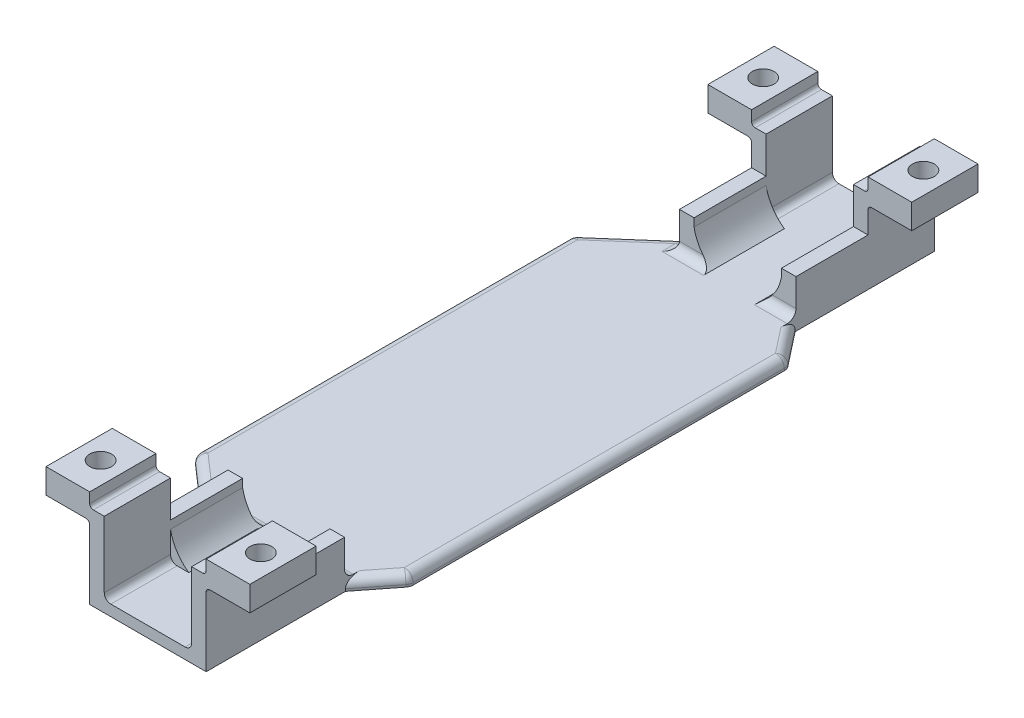
SolidWorks part; units mm, degrees
ref_plane "Front Plane" through (0, 0, 0) normal (0, 0, 1) x (1, 0, 0)
ref_plane "Top Plane" through (0, 0, 0) normal (0, 1, 0) x (1, 0, 0)
ref_plane "Right Plane" through (0, 0, 0) normal (1, 0, 0) x (0, 0, -1)
sketch "Sketch2" plane through (0, 0, 0) normal (0, 1, 0) x (1, 0, 0)
  line L1 (-8, -9.5) -> (8, -9.5)
  line L2 (-8, -9.5) -> (-8, 9.5)
  line L3 (-8, 9.5) -> (8, 9.5)
  line L4 (8, -9.5) -> (8, 9.5)
  line L5 (-8, -9.5) -> (8, 9.5) construction
  line L6 (-8, 9.5) -> (8, -9.5) construction
  point P0 (0, 0)
  dimension "D1" = 16
  dimension "D2" = 19
extrude "Boss-Extrude1" add sketch "Sketch2" along normal blind 13.3
sketch "Sketch3" plane through (0, 13.3, 0) normal (0, 1, 0) x (1, 0, 0)
  line L0 (8, 9.5) -> (-8, 9.5) construction
  line L1 (-6, -9.5) -> (6, -9.5)
  line L2 (-6, -9.5) -> (-6, 9.5)
  line L3 (-6, 9.5) -> (6, 9.5)
  line L4 (6, -9.5) -> (6, 9.5)
  line L5 (-6, -9.5) -> (6, 9.5) construction
  line L6 (-6, 9.5) -> (6, -9.5) construction
  point P0 (0, 0)
  dimension "D1" = 12
extrude "Cut-Extrude1" cut sketch "Sketch3" against normal blind 8.9
fillet "Fillet1" radius 2 2 edges at (-8, 13.3, 0) (8, 13.3, 0)
sketch "Sketch4" plane through (0, 0, 0) normal (1, 0, 0) x (0, 0, -1)
  line L0 (8.8, 0) -> (-8.8, 0) construction
  line L1 (-9.5, 13.3) -> (0.4, 13.3)
  line L2 (-9.5, 13.3) -> (-9.5, 9.4)
  line L3 (-9.5, 9.4) -> (0.4, 9.4)
  line L4 (0.4, 13.3) -> (0.4, 9.4)
  dimension "D1" = 9.9
  dimension "D2" = 9.4
extrude "Cut-Extrude2" cut sketch "Sketch4" against normal through all both and the other way through all
sketch "Sketch5" plane through (0, 0, 0) normal (1, 0, 0) x (0, 0, -1)
  line L0 (8.8, 0) -> (-8.8, 0) construction
  line L1 (-7, 2.7) -> (-3.2, 2.7)
  line L2 (-7, 2.7) -> (-7, 1)
  line L3 (-7, 1) -> (-3.2, 1)
  line L4 (-3.2, 2.7) -> (-3.2, 1)
  line L5 (-9.5, 9.4) -> (-9.5, 0) construction
  dimension "D1" = 3.8
  dimension "D2" = 1.7
  dimension "D3" = 1
  dimension "D4" = 2.5
extrude "Cut-Extrude3" cut sketch "Sketch5" against normal through all both and the other way through all
sketch "Sketch6" plane through (0, 0, 0) normal (0, 1, 0) x (1, 0, 0)
  line L0 (6, 9.5) -> (-6, 9.5) construction
  line L1 (-14, 9.5) -> (14, 9.5)
  line L2 (0, 9.5) -> (0, 0.4)
  line L3 (-14, 0.4) -> (14, 0.4)
  line L4 (14, 9.5) -> (14, 0.4)
  line L6 (0, -3.575) -> (0, 3.575) construction
  line L7 (-14, 9.5) -> (-14, 0.4)
  dimension "D1" = 9.1
  dimension "D2" = 14
extrude "Boss-Extrude2" add sketch "Sketch6" along normal blind 2.5 contours L4 L1 L2 L3 | L1 L7 L3 L2
sketch "Sketch7" plane through (0, 2.5, 0) normal (0, 1, 0) x (1, 0, 0)
  line L0 (-8, 9.5) -> (-8, 0.4) construction
  line L1 (-14, 9.5) -> (-8, 9.5) construction
  line L2 (0, -3.575) -> (0, 3.575) construction
  line L3 (-14, 9.5) -> (-14, 0.4) construction
  circle A0 centre (-11, 5) radius 1.55
  circle A1 centre (11, 5) radius 1.55
  dimension "D1" = 3.1
  dimension "D2" = 3
  dimension "D3" = 4.5
  dimension "D4" = 3
extrude "Cut-Extrude4" cut sketch "Sketch7" against normal through all both and the other way through all
sketch "Sketch14" plane through (0, 0, 0) normal (0, 0, 1) x (1, 0, 0)
  line L1 (-6, 13.3) -> (6, 13.3)
  line L2 (-6, 13.3) -> (-6, 4.4)
  line L3 (-6, 4.4) -> (6, 4.4)
  line L4 (6, 13.3) -> (6, 4.4)
extrude "Boss-Extrude3" add sketch "Sketch14" along normal blind 9.5
sketch "Sketch16" plane through (0, 0, 0) normal (0, 1, 0) x (1, 0, 0)
  line L1 (-14, 9.5) -> (14, 9.5)
  line L2 (-14, 9.5) -> (-14, 0.4)
  line L3 (-14, 0.4) -> (14, 0.4)
  line L4 (14, 9.5) -> (14, 0.4)
extrude "Cut-Extrude10" cut sketch "Sketch16" along normal through all both and the other way through all
sketch "Sketch17" plane through (0, 0, 0) normal (0, 1, 0) x (1, 0, 0)
  line L1 (-8, -9.5) -> (8, -9.5)
  line L2 (-8, -9.5) -> (-8, -71.5)
  line L3 (-8, -71.5) -> (8, -71.5)
  line L4 (8, -9.5) -> (8, -71.5)
  dimension "D1" = 62
  dimension "D2" = 16
extrude "Boss-Extrude5" add sketch "Sketch17" along normal blind 4.4
sketch "Sketch22" plane through (0, 0, 0) normal (0, 1, 0) x (1, 0, 0)
  line L0 (-3.575, 0) -> (3.575, 0) construction
  line L1 (-6, 0.4) -> (6.0328, 0.4)
  line L2 (-6, 0.4) -> (-6, 0)
  line L3 (-6, 0) -> (6.0328, 0)
  line L4 (6.0328, 0.4) -> (6.0328, 0)
extrude "Boss-Extrude7" add sketch "Sketch22" along normal blind 9.4
sketch "Sketch20" plane through (0, 0, 0) normal (0, 1, 0) x (1, 0, 0)
  line L1 (-8, -71.5) -> (8, -71.5)
  line L2 (-8, -71.5) -> (-8, -81.4)
  line L3 (-8, -81.4) -> (8, -81.4)
  line L4 (8, -71.5) -> (8, -81.4)
  dimension "D1" = 9.9
  dimension "D2" = 16
extrude "Boss-Extrude6" add sketch "Sketch20" along normal blind 9.4
sketch "Sketch24" plane through (0, 0, 0) normal (0, 1, 0) x (1, 0, 0)
  line L1 (-8, -81.4) -> (8, -81.4)
  line L2 (-8, -81.4) -> (-8, -90.5)
  line L3 (-8, -90.5) -> (8, -90.5)
  line L4 (8, -81.4) -> (8, -90.5)
  line L5 (8, 0.4) -> (-8, 0.4)
  line L6 (8, 0.4) -> (8, 9.5)
  line L7 (8, 9.5) -> (-8, 9.5)
  line L8 (-8, 0.4) -> (-8, 9.5)
  dimension "D1" = 9.1
  dimension "D2" = 16
  dimension "D3" = 9.1
  dimension "D4" = 16
extrude "Boss-Extrude8" add sketch "Sketch24" along normal blind 4.4
sketch "Sketch21" plane through (0, 0, 0) normal (1, 0, 0) x (0, 0, -1)
  line L0 (8.8, 0) -> (-8.8, 0) construction
  line L1 (-81.4, 0) -> (918.6, 0)
  line L2 (-81.4, 0) -> (-81.4, 2.9)
  line L3 (-81.4, 2.9) -> (918.6, 2.9)
  line L4 (918.6, 0) -> (918.6, 2.9)
  line L5 (-81.4, 9.4) -> (-81.4, 4.4) construction
  line L6 (-71.5, 4.4) -> (-9.5, 4.4) construction
  dimension "D1" = 1.5
  dimension "D2" = 1000
extrude "Cut-Extrude11" cut sketch "Sketch21" against normal through all both and the other way through all
sketch "Sketch15" plane through (0, 0, 0) normal (0, 0, 1) x (1, 0, 0)
  line L0 (0, -3.575) -> (0, 3.575) construction
  line L1 (-6, 4.4) -> (6, 4.4) construction
  line L2 (-6, 4.4) -> (6, 4.4)
  line L7 (-6, 13.3) -> (6, 13.3)
  line L8 (-6, 13.3) -> (-6, 9.4)
  line L9 (-6, 9.4) -> (6, 9.4)
  line L10 (6, 13.3) -> (6, 9.4)
  line L11 (6, 13.3) -> (6, 4.4)
  line L12 (6, 13.3) -> (6, 4.4)
  line L13 (-6, 13.3) -> (-6, 4.4)
  circle A0 centre (0, 9.4) radius 6.1
  dimension "D1" = 12.2
  dimension "D2" = 5
extrude "Cut-Extrude9" cut sketch "Sketch15" against normal blind 1000 and the other way blind 81.4 contours L7 A0 | L9 A0 L7 | L9 A0 L2 | A0 L7 L8
sketch "Sketch25" plane through (0, 4.4, 0) normal (0, 1, 0) x (1, 0, 0)
  line L0 (6, 0.4) -> (8, 0.4) construction
  line L1 (8, -90.5) -> (6, -90.5)
  line L2 (8, -90.5) -> (8, -81.4)
  line L3 (8, -81.4) -> (6, -81.4)
  line L4 (6, -90.5) -> (6, -81.4)
  line L5 (-8, -90.5) -> (-6, -90.5)
  line L6 (-8, -90.5) -> (-8, -81.4)
  line L7 (-8, -81.4) -> (-6, -81.4)
  line L8 (-6, -90.5) -> (-6, -81.4)
  line L9 (-8, 9.5) -> (-6, 9.5)
  line L10 (-8, 9.5) -> (-8, 0.4)
  line L11 (-8, 0.4) -> (-6, 0.4)
  line L12 (-6, 9.5) -> (-6, 0.4)
  line L13 (8, 9.5) -> (6, 9.5)
  line L14 (8, 9.5) -> (8, 0.4)
  line L15 (8, 0.4) -> (6, 0.4)
  line L16 (6, 9.5) -> (6, 0.4)
  line L17 (3.4943, 0.4) -> (8, 0.4) construction
extrude "Boss-Extrude9" add sketch "Sketch25" along normal blind 10
fillet "Fillet4" radius 0.9 4 edges at (6, 4.4, 85.95) (-6, 4.4, 85.95) (-6, 4.4, -4.95) (6, 4.4, -4.95)
sketch "Sketch26" plane through (8, 0, 0) normal (1, 0, 0) x (0, 0, -1)
  line L0 (9.5, 2.9) -> (-81.4, 2.9) construction
  line L1 (-91.3554, -1.7985) -> (-79.9561, -1.7985)
  line L2 (-91.3554, -1.7985) -> (-91.3554, 2.9)
  line L3 (-91.3554, 2.9) -> (-79.9561, 2.9)
  line L4 (-79.9561, -1.7985) -> (-79.9561, 2.9)
extrude "Cut-Extrude12" cut sketch "Sketch26" against normal through all both and the other way through all
sketch "Sketch27" plane through (0, 14.4, 0) normal (0, 1, 0) x (1, 0, 0)
  line L0 (-14, -40.5) -> (16.7963, -40.5)
  line L1 (8, 9.5) -> (14, 9.5)
  line L2 (8, 9.5) -> (8, 0.4)
  line L3 (8, 0.4) -> (14, 0.4)
  line L4 (14, 9.5) -> (14, 0.4)
  line L5 (-8, 9.5) -> (-14, 9.5)
  line L6 (-8, 9.5) -> (-8, 0.4)
  line L7 (-8, 0.4) -> (-14, 0.4)
  line L8 (-14, 9.5) -> (-14, 0.4)
  line L9 (8, -9.5) -> (3.4943, -9.5) construction
  line L10 (0, -7.315) -> (0, 7.315) construction
  line L11 (8, -81.4) -> (14, -81.4)
  line L12 (14, -90.5) -> (14, -81.4)
  line L13 (8, -90.5) -> (14, -90.5)
  line L14 (8, -90.5) -> (8, -81.4)
  line L15 (-8, -81.4) -> (-14, -81.4)
  line L16 (-14, -90.5) -> (-14, -81.4)
  line L17 (-8, -90.5) -> (-14, -90.5)
  line L18 (-8, -90.5) -> (-8, -81.4)
  circle A0 centre (-11, 5) radius 1.5
  circle A1 centre (11, 5) radius 1.5
  circle A2 centre (11, -86) radius 1.5
  circle A3 centre (-11, -86) radius 1.5
  point P16 (0, 0)
  point P18 (-10.6998, 5.4738)
  point P19 (-14, 4.3083)
  line M16 (8, 0.4) -> (8, 9.5)
  dimension "D6" = 3
  dimension "D1" = 9.1
  dimension "D2" = 9.1
  dimension "D3" = 6
  dimension "D4" = 6
  dimension "D5" = 31
  dimension "D7" = 3
  dimension "D8" = 4.5
extrude "Boss-Extrude10" add sketch "Sketch27" along normal blind 1.9 and the other way blind 1.5 contours L14 L13 L12 L11 A2 | L17 L18 L15 L16 A3 | L5 L8 L7 L6 A0 | L4 L1 L3 A1 M16
fillet "Fillet10" radius 0.5 4 edges at (8, 12.9, 85.95) (-8, 12.9, -4.95) (8, 12.9, -4.95) (-8, 12.9, 85.95)
fillet "Fillet11" radius 0.5 4 edges at (8, 14.4, 85.95) (-8, 14.4, 85.95) (-8, 14.4, -4.95) (8, 14.4, -4.95)
sketch "Sketch28" plane through (0, 2.9, 0) normal (0, -1, 0) x (1, 0, 0)
  line L1 (-11.9051, 66.4) -> (11.9051, 66.4)
  line L2 (-11.9051, 66.4) -> (-11.9051, 14.6)
  line L3 (-11.9051, 14.6) -> (11.9051, 14.6)
  line L4 (0, 66.4) -> (0, 14.6)
  line L6 (0, -7.37) -> (0, 7.37) construction
  line L7 (-8.5, 81.4) -> (-14, 81.4) construction
  line L11 (-11.9051, 66.4) -> (-7.9051, 71.5)
  line L12 (-7.9051, 71.5) -> (7.9051, 71.5)
  line L13 (0, 71.5) -> (0, 66.4)
  line L14 (-11.9051, 14.6) -> (-7.9051, 9.5)
  line L15 (-7.9051, 9.5) -> (7.9051, 9.5)
  line L16 (0, 9.5) -> (0, 14.6)
  line L17 (11.9051, 66.4) -> (7.9051, 71.5)
  line L18 (11.9051, 14.6) -> (7.9051, 9.5)
  line L19 (11.9051, 66.4) -> (11.9051, 14.6)
  point P22 (0, 0)
  dimension "D2" = 0
  dimension "D3" = 15
  dimension "D4" = 15
extrude "Boss-Extrude11" add sketch "Sketch28" against normal blind 1.5
fillet "Fillet16" radius 1.2 5 edges at (11.9051, 3.65, 14.6) (11.9051, 3.65, 66.4) (9.9526, 4.4, 68.8895) (11.9051, 4.4, 40.5) (9.9526, 4.4, 12.1105)
sketch "Sketch30" plane through (0, 2.9, 0) normal (0, -1, 0) x (1, 0, 0)
  line L0 (11.9051, 65.9855) -> (11.9051, 15.0145) construction
  line L1 (-11.9051, 14.6) -> (-17.5949, 14.6)
  line L2 (-11.9051, 14.6) -> (-11.9051, 66.4)
  line L3 (-11.9051, 66.4) -> (-17.5949, 66.4)
  line L4 (-17.5949, 14.6) -> (-17.5949, 66.4)
  line L5 (-11.9051, 66.4) -> (-11.9051, 74.2359)
  line L8 (-8, 71.379) -> (-14.2361, 71.379)
  line L9 (-17.5949, 66.4) -> (-11.9051, 71.379)
  line L10 (-11.9051, 71.379) -> (-8, 74.7964)
  line L11 (-8, 71.379) -> (-8, 90.5) construction
  line L12 (-8, 9.621) -> (-18.0983, 9.621)
  line L13 (-11.9051, 14.6) -> (-11.9051, 6.3568)
  line L14 (-17.5949, 14.6) -> (-11.9051, 9.621)
  line L15 (-11.9051, 9.621) -> (-8, 6.2036)
  line L16 (-8, -9.5) -> (-8, 9.621) construction
  line L17 (-8, 6.2036) -> (-8, 9.621)
  line L18 (-8, 71.379) -> (-8, 74.7964)
  line L19 (-8, 71.379) -> (-8, 9.621)
  point P8 (11.9051, 40.5)
  line M14 (-8, 90.5) -> (-8, 71.379)
  line M15 (-8, 71.379) -> (-11.9051, 66.4)
  line M16 (-11.9051, 66.4) -> (-11.9051, 14.6)
  line M17 (-11.9051, 14.6) -> (-8, 9.621)
  line M18 (-8, 9.621) -> (-8, -9.5)
  dimension "D1" = 0
  dimension "D2" = 29.5
extrude "Boss-Extrude12" add sketch "Sketch30" against normal blind 1.5 contours L4 L1 L3 M16 | L1 L14 L13 | L13 L12 M17 | L9 L3 L5 | L8 L5 M15 | L12 L15 M18 | L10 L8 M14
fillet "Fillet19" radius 1.2 9 edges at (-17.5949, 3.65, 14.6) (-17.5949, 3.65, 66.4) (-8, 3.65, 74.7964) (-12.7974, 4.4, 10.4018) (-8, 3.65, 6.2036) (-17.5949, 4.4, 40.5) (-12.7974, 4.4, 70.5982) (-8, 4.4, 73.1482) (-8, 4.4, 7.8518)
fillet "Fillet20" radius 1.2 4 edges at (5.7471, 4.4, 9.5) (-6.3471, 4.4, 9.5) (-6.3471, 4.4, 71.5) (5.7471, 4.4, 71.5)
